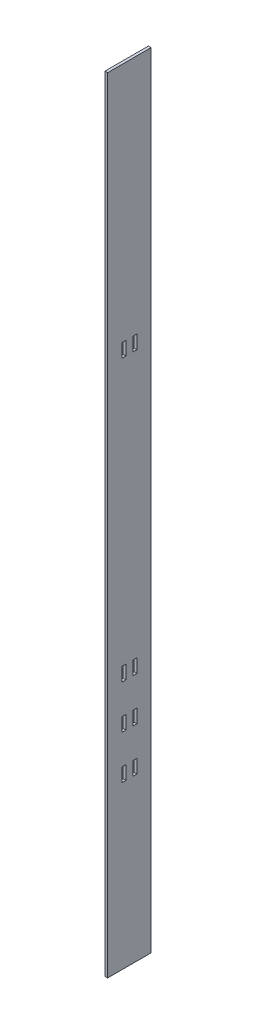
SolidWorks part; units mm, degrees
ref_plane "Front Plane" through (0, 0, 0) normal (0, 0, 1) x (1, 0, 0)
ref_plane "Top Plane" through (0, 0, 0) normal (0, 1, 0) x (1, 0, 0)
ref_plane "Right Plane" through (0, 0, 0) normal (1, 0, 0) x (0, 0, -1)
sketch "Sketch1" plane through (0, 0, 0) normal (1, 0, 0) x (0, 0, -1)
  line L1 (-25.4, 457.2) -> (25.4, 457.2)
  line L2 (-25.4, 457.2) -> (-25.4, -457.2)
  line L3 (-25.4, -457.2) -> (25.4, -457.2)
  line L4 (25.4, 457.2) -> (25.4, -457.2)
  line L5 (-25.4, 457.2) -> (25.4, -457.2) construction
  line L6 (-25.4, -457.2) -> (25.4, 457.2) construction
  point P0 (0, 0)
  dimension "D1" = 914.4
  dimension "D2" = 50.8
extrude "Boss-Extrude1" add sketch "Sketch1" along normal blind 3.175
sketch "Sketch2" plane through (3.175, 0, 0) normal (1, 0, 0) x (0, 0, -1)
  line L0 (-25.4, -457.2) -> (25.4, -457.2) construction
  line L1 (4, -201.6125) -> (8.7625, -201.6125)
  line L2 (4, -201.6125) -> (4, -217.4875)
  line L3 (4, -217.4875) -> (8.7625, -217.4875)
  line L4 (8.7625, -201.6125) -> (8.7625, -217.4875)
  line L5 (4, -201.6125) -> (8.7625, -217.4875) construction
  line L6 (4, -217.4875) -> (8.7625, -201.6125) construction
  point P0 (6.3813, -209.55)
  dimension "D1" = 4.7625
  dimension "D2" = 15.875
  dimension "D3" = 239.7125
  dimension "D4" = 4
extrude "Cut-Extrude1" cut sketch "Sketch2" against normal through all
mirror "Mirror1" about plane through (0, 0, 0) normal (0, 0, 1) of "Cut-Extrude1"
pattern_linear "LPattern1" count 2 spacing 50.8 along (0, 1, 0) count 2 spacing 50.8 along (0, -1, 0) of "Mirror1"
sketch "Sketch3" plane through (3.175, 0, 0) normal (1, 0, 0) x (0, 0, -1)
  line L0 (8.7625, -150.8125) -> (4, -150.8125) construction
  line L1 (4, 176.2125) -> (8.7625, 176.2125)
  line L2 (4, 176.2125) -> (4, 160.3375)
  line L3 (4, 160.3375) -> (8.7625, 160.3375)
  line L4 (8.7625, 176.2125) -> (8.7625, 160.3375)
  line L5 (4, 176.2125) -> (8.7625, 160.3375) construction
  line L6 (4, 160.3375) -> (8.7625, 176.2125) construction
  line L7 (8.7625, -166.6875) -> (8.7625, -150.8125) construction
  line L8 (4, -150.8125) -> (4, -166.6875) construction
  line L9 (0, 0) -> (0, 53.0447) construction
  line L10 (-4, 160.3375) -> (-8.7625, 176.2125) construction
  line L11 (-4, 176.2125) -> (-8.7625, 160.3375) construction
  line L12 (-8.7625, 176.2125) -> (-8.7625, 160.3375)
  line L13 (-4, 160.3375) -> (-8.7625, 160.3375)
  line L14 (-4, 176.2125) -> (-4, 160.3375)
  line L15 (-4, 176.2125) -> (-8.7625, 176.2125)
  point P0 (6.3812, 168.275)
  point P12 (6.3812, 160.3375)
  point P19 (-6.3812, 168.275)
  dimension "D1" = 311.15
extrude "Cut-Extrude2" cut sketch "Sketch3" against normal through all
